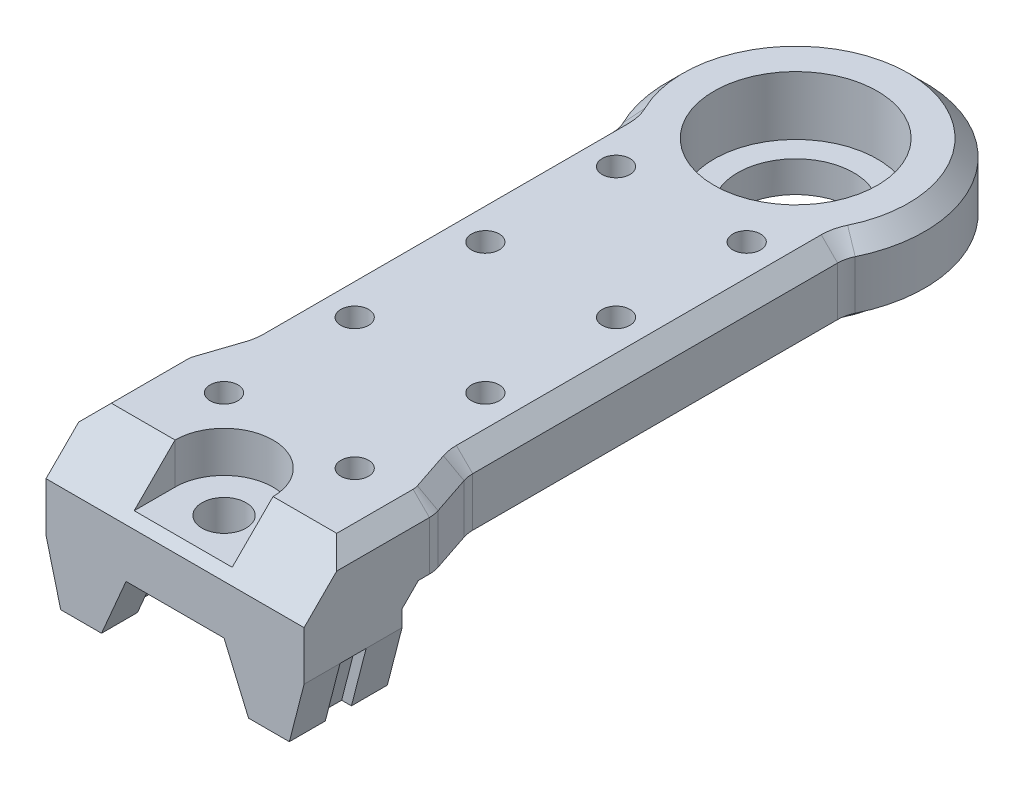
SolidWorks part; units mm, degrees
material "ABS"
ref_plane "正面" through (0, 0, 0) normal (0, 0, 1) x (1, 0, 0)
ref_plane "平面" through (0, 0, 0) normal (0, 1, 0) x (1, 0, 0)
ref_plane "右側面" through (0, 0, 0) normal (1, 0, 0) x (0, 0, -1)
sketch "ｽｹｯﾁ1" plane through (0, 0, 0) normal (0, 1, 0) x (1, 0, 0)
  line L2 (-7.9, 0) -> (-7.9, -38)
  line L3 (-7.9, -38) -> (7.9, -38)
  line L4 (7.9, 0) -> (7.9, -38)
  line L5 (-7.9, 0) -> (7.9, -38) construction
  line L6 (-7.9, -38) -> (7.9, 0) construction
  arc A0 (7.9, 0) -> (-7.9, 0) centre (0, 0) ccw
  point P7 (0, -19)
  dimension "D2" = 0
  dimension "D4" = 38
  dimension "D3" = 15.8
extrude "ﾎﾞｽ - 押し出し1" add sketch "ｽｹｯﾁ1" along normal blind 4
sketch "ｽｹｯﾁ4" plane through (0, 0, 38) normal (0, 0, 1) x (1, 0, 0)
  line L1 (-7, -5.5) -> (-4.5, -5.5)
  line L2 (-4.5, -5.5) -> (-3, -2)
  line L3 (-3, -2) -> (3, -2)
  line L4 (3, -2) -> (4.5, -5.5)
  line L5 (4.5, -5.5) -> (7, -5.5)
  line L7 (7.9, 0) -> (-7.9, 0)
  line L8 (-7, -5.5) -> (-7.9, -2)
  line L9 (-7.9, -2) -> (-7.9, 0)
  line L10 (7.9, 0) -> (7.9, -2)
  line L11 (7.9, -2) -> (7, -5.5)
  dimension "D1" = 5.5
  dimension "D2" = 3.5
  dimension "D3" = 3
  dimension "D4" = 7
  dimension "D5" = 2.5
  dimension "D9" = 2
  dimension "D10" = 2
extrude "ﾎﾞｽ - 押し出し3" add sketch "ｽｹｯﾁ4" against normal blind 6
chamfer "面取り1" distance 3 angle 45 1 edges at (0, 4, 38)
sketch "ｽｹｯﾁ5" plane through (0, 4, 0) normal (0, 1, 0) x (1, 0, 0)
  line L0 (-4, -31) -> (4, -31) construction
  line L1 (7.9, -38) -> (-7.9, -38) construction
  circle A0 centre (-4, -31) radius 0.85
  circle A1 centre (4, -31) radius 0.85
  dimension "D1" = 1.7
  dimension "D2" = 1.7
  dimension "D4" = 4
  dimension "D3" = 8
  dimension "D5" = 7
extrude "ｶｯﾄ - 押し出し1" cut sketch "ｽｹｯﾁ5" against normal blind 4
pattern_linear "直線ﾊﾟﾀｰﾝ1" count 4 spacing 8 along (0, 0, -1) of "ｶｯﾄ - 押し出し1"
sketch "ｽｹｯﾁ6" plane through (0, 4, 0) normal (0, 1, 0) x (1, 0, 0)
  line L0 (-3, -35) -> (-3, -39)
  line L1 (-3, -39) -> (3, -39)
  line L2 (3, -39) -> (3, -35)
  line L3 (7.9, -38) -> (-7.9, -38) construction
  arc A0 (3, -35) -> (-3, -35) centre (0, -35) ccw
  dimension "D1" = 6
  dimension "D3" = 3
  dimension "D2" = 0
  dimension "D4" = 4
extrude "ｶｯﾄ - 押し出し2" cut sketch "ｽｹｯﾁ6" against normal blind 2.5
sketch "ｽｹｯﾁ7" plane through (0, 1.5, 0) normal (0, 1, 0) x (1, 0, 0)
  circle A0 centre (0, -35) radius 1.35
  dimension "D1" = 2.7
extrude "ｶｯﾄ - 押し出し3" cut sketch "ｽｹｯﾁ7" against normal up to next
sketch "ｽｹｯﾁ8" plane through (0, 0, 0) normal (0, -1, 0) x (1, 0, 0)
  circle A0 centre (0, 0) radius 6
  dimension "D1" = 12
extrude "ﾎﾞｽ - 押し出し4" add sketch "ｽｹｯﾁ8" along normal blind 1.5
fillet "ﾌｨﾚｯﾄ1" radius 0.5 1 edges at (0, 0, 6)
sketch "ｽｹｯﾁ9" plane through (0, 4, 0) normal (0, 1, 0) x (1, 0, 0)
  circle A0 centre (0, 0) radius 5
  dimension "D1" = 10
extrude "ｶｯﾄ - 押し出し4" cut sketch "ｽｹｯﾁ9" against normal blind 3.6
sketch "ｽｹｯﾁ10" plane through (0, 0.4, 0) normal (0, 1, 0) x (1, 0, 0)
  circle A0 centre (0, 0) radius 3.55
  dimension "D1" = 7.1
extrude "ｶｯﾄ - 押し出し5" cut sketch "ｽｹｯﾁ10" against normal blind 3.6
ref_plane "平面1" through (0, 0, 35) normal (0, 0, 1) x (1, 0, 0)
sketch "ｽｹｯﾁ11" plane through (0, 0, 35) normal (0, 0, 1) x (1, 0, 0)
  line L0 (3, -2) -> (4.5, -5.5)
  line L1 (3, -2) -> (3.6, -2)
  line L2 (4.5, -5.5) -> (5.1, -5.5)
  line L3 (3.6, -2) -> (5.1, -5.5)
  line L4 (3, -2) -> (5.1, -5.5) construction
  line L5 (4.5, -5.5) -> (3.6, -2) construction
  line L6 (4.5, -5.5) -> (7, -5.5) construction
  line L7 (7.9, -2) -> (7, -5.5)
  line L8 (7.9, -2) -> (7.3, -2)
  line L9 (7, -5.5) -> (6.4, -5.5)
  line L10 (7.3, -2) -> (6.4, -5.5)
  line L11 (7.9, -2) -> (6.4, -5.5) construction
  line L12 (7, -5.5) -> (7.3, -2) construction
  point P5 (4.05, -3.75)
  point P14 (7.15, -3.75)
  dimension "D1" = 0.6
extrude "ｶｯﾄ - 押し出し6" cut sketch "ｽｹｯﾁ11" against normal mid plane 1.6
mirror "ﾐﾗｰ1" about plane through (0, 0, 0) normal (1, 0, 0) of "ｶｯﾄ - 押し出し6"
sketch "ｽｹｯﾁ12" plane through (0, 4, 0) normal (0, 1, 0) x (1, 0, 0)
  line L0 (-7.9, 0) -> (-7.9, -30)
  line L1 (-7.9, 0) -> (-7.9, -35) construction
  line L2 (-7.9, -30) -> (-6.9, -27)
  line L3 (-6.9, -27) -> (-6.9, -3.8471)
  line L4 (7.9, -38) -> (-7.9, -38) construction
  arc A0 (-7.9, 0) -> (-6.9, -3.8471) centre (0, 0) ccw
  arc A1 (7.9, 0) -> (-7.9, 0) centre (0, 0) ccw construction
  dimension "D1" = 6.9
  dimension "D2" = 11
  dimension "D3" = 3
extrude "ｶｯﾄ - 押し出し7" cut sketch "ｽｹｯﾁ12" against normal through all
mirror "ﾐﾗｰ2" about plane through (0, 0, 0) normal (1, 0, 0) of "ｶｯﾄ - 押し出し7"
fillet "ﾌｨﾚｯﾄ2" radius 2 6 edges at (7.9, 2, 30) (6.9, 2, 27) (6.9, 2, 3.8471) (-7.9, 2, 30) (-6.9, 2, 27) (-6.9, 2, 3.8471)
chamfer "面取り2" distance 1 angle 45 14 edges at (-7.9, 4, 32.6623) (0, 4, -7.9) (7.9, 4, 32.6623) (0, 0, 32) (-7.8742, 4, 30.0042) (-7.4, 4, 28.5) (-6.9258, 4, 26.9958) (-6.9, 4, 15.5057) (-6.9512, 4, 3.8864) (6.9512, 4, 3.8864) (6.9, 4, 15.5057) (6.9258, 4, 26.9958) (7.4, 4, 28.5) (7.8742, 4, 30.0042)
